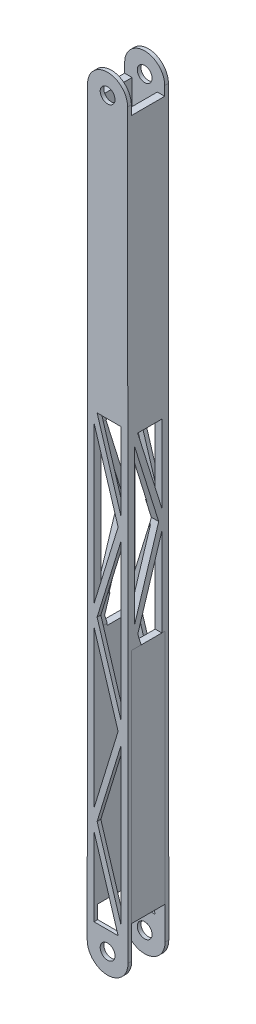
SolidWorks part; units mm, degrees
note: The reader was unsure of these and kept them because the rebuilt part matched: shared geometry of "Sketch1<3>", "Sketch1<4>".
ref_plane "Front Plane" through (0, 0, 0) normal (0, 0, 1) x (1, 0, 0)
ref_plane "Top Plane" through (0, 0, 0) normal (0, 1, 0) x (1, 0, 0)
ref_plane "Right Plane" through (0, 0, 0) normal (1, 0, 0) x (0, 0, -1)
sketch "Sketch1" plane through (0, 0, 0) normal (0, 0, 1) x (1, 0, 0)
  line L0 (0, 0) -> (0, 1000) construction
  line L1 (27, 1000) -> (27.5, 0)
  line L2 (-27, 1000) -> (-27.5, 0)
  line L3 (-27.3185, 362.9766) -> (-17.3185, 362.9766)
  line L4 (-17.3185, 362.9766) -> (-17.0063, 987.4191)
  line L5 (-27.0063, 987.4191) -> (-17.0063, 987.4191)
  line L6 (-16.9895, 1020.9847) -> (-16.7436, 1512.8404)
  line L7 (27.0063, 987.4191) -> (17.0063, 987.4191)
  line L8 (27.3185, 362.9766) -> (17.3185, 362.9766)
  line L9 (17.3185, 362.9766) -> (17.0063, 987.4191)
  circle A0 centre (0, 0) radius 10
  arc A1 (-27.5, 0) -> (27.5, 0) centre (0, 0) ccw
  arc A2 (27, 1000) -> (-27, 1000) centre (0, 1000) ccw
  circle A3 centre (0, 1000) radius 10
  dimension "D1" = 20
  dimension "D2" = 55
  dimension "D4" = 20
  dimension "D5" = 54
  dimension "D3" = 1000
  dimension "D6" = 10
extrude "Boss-Extrude2" add sketch "Sketch1" along normal blind 5
extrude "Boss-Extrude3" add sketch "Sketch1<3>" along normal blind 55 contours L9 L8 L1 L7 | L5 L2 L3 L4
sketch "Sketch1<3>" plane through (0, 0, 0) normal (0, 0, 1) x (1, 0, 0) same geometry as "Sketch1"
extrude "Boss-Extrude4" add sketch "Sketch1<4>" along normal blind 5 from offset 50
sketch "Sketch1<4>" plane through (0, 0, 0) normal (0, 0, 1) x (1, 0, 0) same geometry as "Sketch1"
sketch "Sketch3" plane through (27.5, 0.0137, 0) normal (1, 0.0005, 0) x (0, 0, -1)
  line L0 (-9.1513, 612.558) -> (-9.1513, 25.6)
  line L1 (-50, 987.4054) -> (-5, 987.4054) construction
  line L2 (-27.5, 987.4054) -> (-27.5, 612.558) construction
  line L3 (-9.1513, 612.558) -> (-45.8487, 612.558)
  line L4 (-45.8487, 612.558) -> (-9.1513, 495.166) construction
  line L5 (-9.1513, 25.6) -> (-45.8487, 25.6)
  line L6 (-45.8487, 612.558) -> (-45.8487, 25.6)
  line L7 (-27.5, 25.6) -> (-27.5, 0) construction
  line L8 (-9.1513, 495.166) -> (-45.8487, 495.166) construction
  line L9 (-45.8487, 377.774) -> (-9.1513, 495.166) construction
  line L10 (-45.8487, 377.774) -> (-9.1513, 377.774) construction
  line L11 (-45.8487, 377.774) -> (-9.1513, 260.382) construction
  line L12 (-9.1513, 260.382) -> (-45.8487, 260.382) construction
  line L13 (-45.8487, 142.99) -> (-9.1513, 260.382) construction
  line L14 (-45.8487, 142.99) -> (-9.1513, 142.99) construction
  line L15 (-45.8487, 142.99) -> (-9.1513, 25.598) construction
  line L16 (-41.6579, 612.558) -> (-9.1513, 508.5722)
  line L17 (-45.8487, 599.1517) -> (-13.3421, 495.166)
  line L18 (-41.6579, 377.774) -> (-9.1513, 481.7597)
  line L19 (-45.8487, 391.1802) -> (-13.3421, 495.166)
  line L20 (-41.6579, 377.774) -> (-9.1513, 273.7882)
  line L21 (-45.8487, 364.3677) -> (-13.3421, 260.382)
  line L22 (-45.8487, 156.3962) -> (-13.3421, 260.382)
  line L23 (-41.6579, 142.99) -> (-9.1513, 246.9757)
  line L24 (-41.6579, 142.99) -> (-9.1513, 39.0042)
  line L25 (-45.8487, 129.5837) -> (-13.3421, 25.598)
  dimension "D1" = 117.392
  dimension "D2" = 4
  dimension "D3" = 4
sketch "Sketch4" plane through (0, 0, 55) normal (0, 0, 1) x (1, 0, 0)
  line L0 (0, 1027) -> (0, 622.1823) construction
  line L1 (0, 990) -> (0, 622.1823) construction
  line L2 (-18.35, 622.1823) -> (18.35, 502.8923) construction
  line L3 (18.35, 622.1823) -> (-18.35, 622.1823)
  line L4 (18.35, 502.8923) -> (-18.35, 502.8923) construction
  line L5 (18.35, 25.7331) -> (-18.35, 25.7331)
  line L6 (-18.35, 622.1823) -> (-18.35, 25.7331)
  line L7 (18.35, 622.1823) -> (18.35, 25.7331)
  line L8 (0, 25.7331) -> (0, -27.5) construction
  line L9 (0, 25.7331) -> (0, 10) construction
  line L10 (-18.35, 383.6023) -> (18.35, 502.8923) construction
  line L11 (-18.35, 383.6023) -> (18.35, 383.6023)
  line L12 (-18.35, 383.6023) -> (18.35, 264.3123) construction
  line L13 (18.35, 264.3123) -> (-18.35, 264.3123) construction
  line L14 (-18.35, 145.0223) -> (18.35, 264.3123) construction
  line L15 (-18.35, 145.0223) -> (18.35, 145.0223) construction
  line L16 (-18.35, 145.0223) -> (18.35, 25.7323) construction
  line L17 (-14.165, 622.1823) -> (18.35, 516.4953)
  line L18 (-18.35, 608.5792) -> (14.165, 502.8923)
  line L19 (-18.35, 397.2053) -> (14.165, 502.8923)
  line L20 (-14.165, 383.6023) -> (18.35, 489.2892)
  line L21 (-14.165, 383.6023) -> (18.35, 277.9153)
  line L22 (-18.35, 369.9992) -> (14.165, 264.3123)
  line L23 (-18.35, 158.6253) -> (14.165, 264.3123)
  line L24 (-14.165, 145.0223) -> (18.35, 250.7092)
  line L25 (-14.165, 145.0223) -> (18.35, 39.3353)
  line L26 (-18.35, 131.4192) -> (14.165, 25.7323)
  line L27 (-18.35, 860.7623) -> (18.35, 860.7623)
  line L28 (18.35, 741.4723) -> (-18.35, 741.4723) construction
  line L29 (-14.165, 860.7623) -> (18.35, 755.0753)
  line L30 (-18.35, 847.1592) -> (14.165, 741.4723)
  line L31 (-18.35, 635.7853) -> (14.165, 741.4723)
  line L32 (-14.165, 622.1823) -> (18.35, 727.8692)
  line L33 (-14.165, 860.7623) -> (18.35, 966.4492)
  line L34 (-18.35, 874.3653) -> (14.165, 980.0523)
  line L35 (18.35, 622.1823) -> (18.35, 980.0523)
  line L36 (-18.35, 622.1823) -> (-18.35, 980.0523)
  line L37 (18.35, 980.0523) -> (-18.35, 980.0523)
  arc A0 (27, 1000) -> (-27, 1000) centre (0, 1000) ccw construction
  arc A1 (-27.5, 0) -> (27.5, 0) centre (0, 0) ccw construction
  circle A6 centre (0, 1000) radius 10 construction
  circle A7 centre (0, 0) radius 10 construction
  dimension "D1" = 119.29
  dimension "D2" = 4
  dimension "D3" = 4
extrude "Cut-Extrude2" cut sketch "Sketch3" against normal through all both and the other way through all contours L23 L24 L0 | L25 L6 L5 | L6 L22 L21 | L18 L20 L0 | L3 L16 L0 | L6 L19 L17
extrude "Cut-Extrude4" cut sketch "Sketch4" against normal through all both and the other way through all contours L6 L23 L22 | L11 L21 L7 | L24 L25 L7 | L6 L19 L18 | L20 L11 L7 | L3 L17 L7 | L26 L6 L5
fillet "Fillet1" [suppressed] radius 11
fillet "Fillet2" [suppressed] radius 11
sketch "Sketch5" plane through (0, 362.9766, 0) normal (0, -1, 0) x (1, 0, 0)
  line L0 (-22.8343, 50) -> (-22.8343, 5) construction
  line L1 (-27.3185, 50) -> (-18.35, 50) construction
  line L2 (-27.3185, 5) -> (-18.35, 5) construction
  line L3 (22.8343, 50) -> (22.8343, 5) construction
  line L4 (27.3185, 50) -> (18.35, 50) construction
  line L5 (27.3185, 5) -> (18.35, 5) construction
  line L7 (-18.35, 50) -> (-27.3185, 50)
  line L8 (-18.35, 50) -> (-18.35, 5)
  line L9 (-18.35, 5) -> (-27.3185, 5)
  line L10 (-27.3185, 50) -> (-27.3185, 5)
  line L11 (-18.35, 50) -> (-27.3185, 5) construction
  line L12 (-18.35, 5) -> (-27.3185, 50) construction
  line L13 (18.35, 50) -> (27.3185, 50)
  line L14 (18.35, 50) -> (18.35, 5)
  line L15 (18.35, 5) -> (27.3185, 5)
  line L16 (27.3185, 50) -> (27.3185, 5)
  line L17 (18.35, 50) -> (27.3185, 5) construction
  line L18 (18.35, 5) -> (27.3185, 50) construction
  point P12 (-22.8343, 27.5)
  point P18 (22.8343, 27.5)
extrude "Boss-Extrude5" add sketch "Sketch5" along normal blind 319
